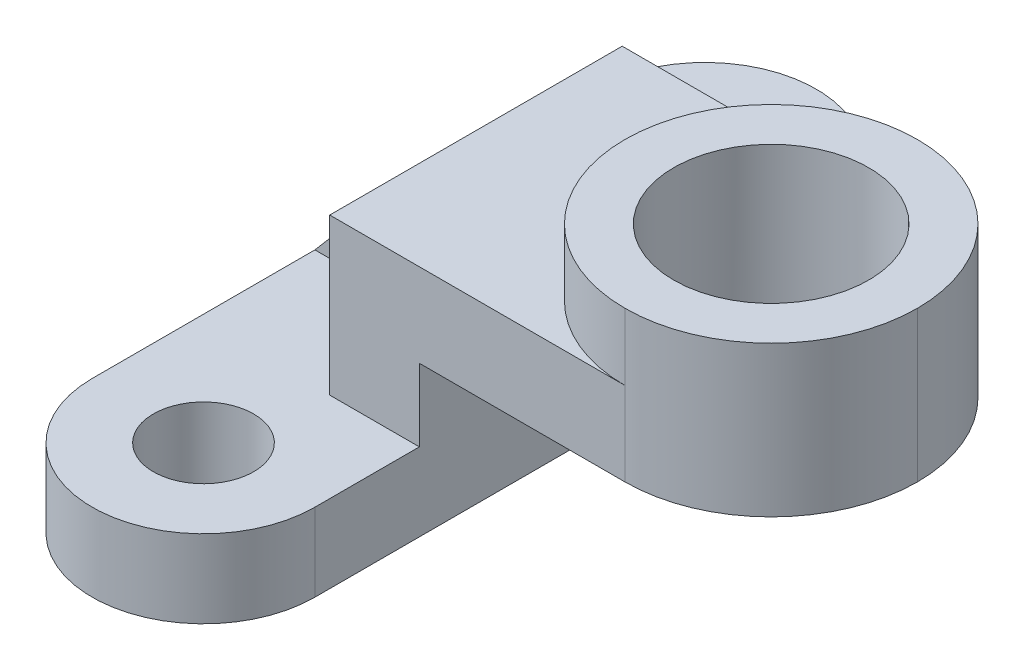
SolidWorks part; units mm, degrees
ref_plane "정면" through (0, 0, 0) normal (0, 0, 1) x (1, 0, 0)
ref_plane "윗면" through (0, 0, 0) normal (0, 1, 0) x (1, 0, 0)
ref_plane "우측면" through (0, 0, 0) normal (1, 0, 0) x (0, 0, -1)
sketch "스케치1" plane through (0, 0, 0) normal (0, 0, 1) x (1, 0, 0)
  line L0 (-68.9045, -51.4852) -> (-68.9045, 4.5148)
  line L1 (-68.9045, 4.5148) -> (-15.4045, 4.5148)
  line L2 (-15.4045, 4.5148) -> (-15.4045, 28.5148)
  line L3 (-15.4045, 28.5148) -> (89.5955, 28.5148)
  line L4 (89.5955, 28.5148) -> (89.5955, -25.4852)
  line L5 (89.5955, -25.4852) -> (-36.7311, -25.4852)
  line L6 (-36.7311, -25.4852) -> (-36.7311, -51.4852)
  line L7 (-36.7311, -51.4852) -> (-68.9045, -51.4852)
  dimension "D1" = 105
  dimension "D2" = 24
  dimension "D3" = 56
  dimension "D4" = 26
  dimension "D5" = 158.5
extrude "보스-돌출1" add sketch "스케치1" along normal mid plane 105
fillet "필렛1" radius 52.5 4 edges at (-15.4045, 16.5148, -52.5) (-15.4045, 16.5148, 52.5) (89.5955, 1.5148, 52.5) (89.5955, 1.5148, -52.5)
sketch "스케치2" plane through (0, 28.5148, 0) normal (0, 1, 0) x (1, 0, 0)
  circle A0 centre (37.0955, 0) radius 35
  dimension "D1" = 70
extrude "컷-돌출1" cut sketch "스케치2" against normal blind 105
sketch "스케치3" plane through (0, -51.4852, 0) normal (0, -1, 0) x (1, 0, 0)
  line L0 (-76.7311, 90) -> (-76.7311, -90) construction
  line L1 (-36.7311, 90) -> (-36.7311, -90)
  line L2 (-116.7311, 90) -> (-116.7311, -90)
  line L6 (-36.7311, 52.5) -> (-36.7311, -52.5) construction
  arc A0 (-36.7311, 90) -> (-116.7311, 90) centre (-76.7311, 90) ccw
  arc A1 (-116.7311, -90) -> (-36.7311, -90) centre (-76.7311, -90) ccw
  circle A2 centre (-76.7311, 90) radius 18
  circle A3 centre (-76.7311, -90) radius 18
  point P2 (-76.7311, 0)
  point P11 (0, 0)
  dimension "D2" = 40
  dimension "D3" = 36
  dimension "D1" = 180
extrude "보스-돌출2" add sketch "스케치3" along normal blind 28
ref_plane "평면1" through (0, 0, 0) normal (0, 0, 1) x (1, 0, 0)
sketch "스케치5" plane through (0, 0, 0) normal (0, 0, 1) x (1, 0, 0)
  line L0 (-68.9045, 4.5148) -> (-116.7311, -51.4852)
rib "보강대1" sketch "스케치5" sketch "스케치5" thickness 20 extrusion direction parallel to sketch draft on no parameters "D1"=20
